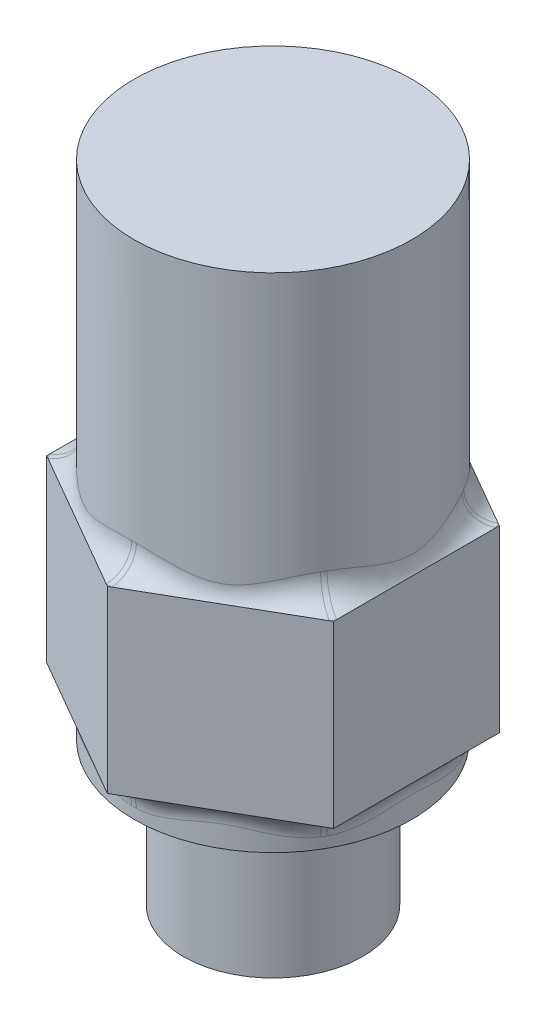
SolidWorks part; units mm, degrees
ref_plane "Спереди" through (0, 0, 0) normal (0, 0, 1) x (1, 0, 0)
ref_plane "Сверху" through (0, 0, 0) normal (0, 1, 0) x (1, 0, 0)
ref_plane "Справа" through (0, 0, 0) normal (1, 0, 0) x (0, 0, -1)
sketch "Эскиз1" plane through (0, 0, 0) normal (0, 1, 0) x (1, 0, 0)
  circle A0 centre (0, 0) radius 2.5
  dimension "D1" = 5
extrude "Бобышка-Вытянуть1" add sketch "Эскиз1" along normal blind 4
sketch "Эскиз3" plane through (0, 4, 0) normal (0, 1, 0) x (1, 0, 0)
  circle A0 centre (0, 0) radius 3.875
  dimension "D1" = 7.75
extrude "Бобышка-Вытянуть2" add sketch "Эскиз3" along normal blind 1
sketch "Эскиз4" plane through (0, 5, 0) normal (0, 1, 0) x (1, 0, 0)
  line L1 (0, -4.6188) -> (4, -2.3094)
  line L2 (4, -2.3094) -> (4, 2.3094)
  line L3 (4, 2.3094) -> (0, 4.6188)
  line L4 (0, 4.6188) -> (-4, 2.3094)
  line L5 (-4, 2.3094) -> (-4, -2.3094)
  line L6 (-4, -2.3094) -> (0, -4.6188)
  circle A0 centre (0, 0) radius 4 construction
  dimension "D1" = 8
extrude "Бобышка-Вытянуть3" add sketch "Эскиз4" along normal blind 5
sketch "Эскиз5" plane through (0, 10, 0) normal (0, 1, 0) x (1, 0, 0)
  circle A0 centre (0, 0) radius 3.875
  dimension "D1" = 7.75
extrude "Бобышка-Вытянуть4" add sketch "Эскиз5" along normal blind 8
fillet "Скругление1" radius 0.7 1 edges at (0, 10, 3.875)
fillet "Скругление2" radius 0.7 1 edges at (0, 5, 3.875)
